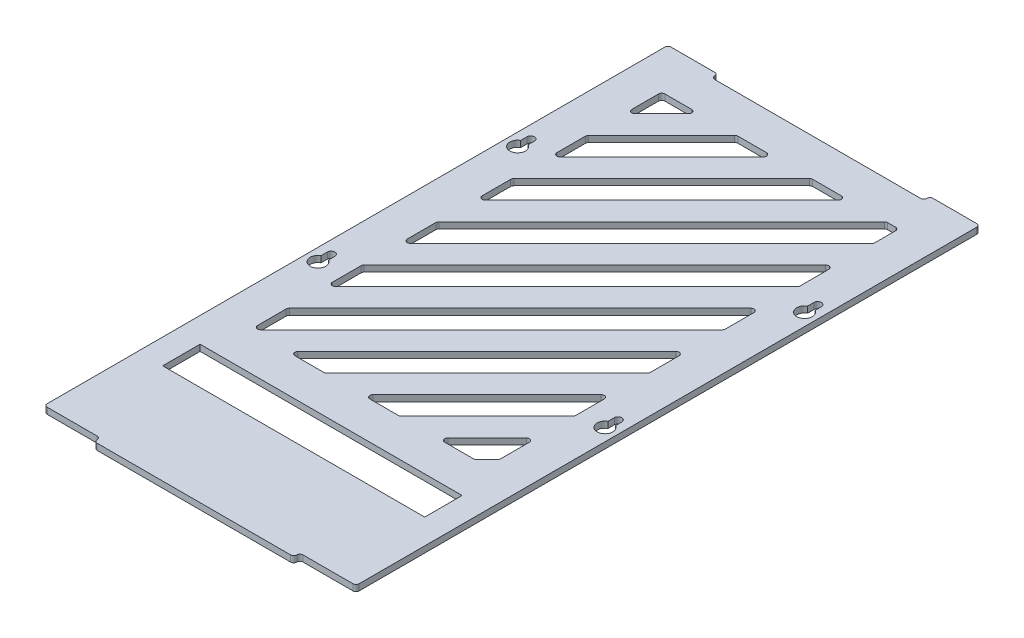
SolidWorks part; units mm, degrees
ref_plane "Front Plane" through (0, 0, 0) normal (0, 0, 1) x (1, 0, 0)
ref_plane "Top Plane" through (0, 0, 0) normal (0, 1, 0) x (1, 0, 0)
ref_plane "Right Plane" through (0, 0, 0) normal (1, 0, 0) x (0, 0, -1)
sketch "Sketch1" plane through (0, 0, 0) normal (0, 1, 0) x (1, 0, 0)
  line L0 (130.175, 0) -> (158.75, 0)
  line L1 (0, 0) -> (28.575, 0)
  line L2 (0, 0) -> (0, 317.5)
  line L3 (0, 317.5) -> (158.75, 317.5)
  line L4 (158.75, 0) -> (158.75, 317.5)
  line L6 (28.575, 0) -> (28.575, -3.175)
  line L7 (28.575, -3.175) -> (130.175, -3.175)
  line L8 (130.175, 0) -> (130.175, -3.175)
  point P9 (79.375, -3.175)
  point P10 (79.375, 317.5)
  dimension "D1" = 158.75
  dimension "D2" = 317.5
  dimension "D3" = 3.175
  dimension "D4" = 101.6
extrude "Boss-Extrude1" add sketch "Sketch1" along normal blind 3.175
sketch "Sketch2" plane through (0, 3.175, 0) normal (0, 1, 0) x (1, 0, 0)
  line L0 (158.75, 317.5) -> (0, 317.5) construction
  line L1 (25.4, 317.5) -> (133.35, 317.5)
  line L2 (25.4, 317.5) -> (25.4, 314.325)
  line L3 (25.4, 314.325) -> (133.35, 314.325)
  line L4 (133.35, 317.5) -> (133.35, 314.325)
  point P6 (79.375, 317.5)
  point P7 (79.375, 317.5)
  dimension "D1" = 107.95
  dimension "D2" = 3.175
extrude "Cut-Extrude1" cut sketch "Sketch2" against normal through all
sketch "Sketch3" plane through (0, 3.175, 0) normal (0, 1, 0) x (1, 0, 0)
  line L0 (25.4, 314.325) -> (133.35, 314.325) construction
  line L1 (12.7, 66.675) -> (146.05, 66.675)
  line L2 (12.7, 66.675) -> (12.7, 47.625)
  line L3 (12.7, 47.625) -> (146.05, 47.625)
  line L4 (146.05, 66.675) -> (146.05, 47.625)
  point P7 (79.375, 314.325)
  point P8 (79.375, 66.675)
  dimension "D1" = 133.35
  dimension "D2" = 19.05
  dimension "D3" = 47.625
extrude "Cut-Extrude2" cut sketch "Sketch3" against normal through all
fillet "Fillet1" radius 1.5875 12 edges at (25.4, 1.5875, -314.325) (25.4, 1.5875, -317.5) (0, 1.5875, -317.5) (0, 1.5875, 0) (28.575, 1.5875, 0) (28.575, 1.5875, 3.175) (130.175, 1.5875, 3.175) (130.175, 1.5875, 0) (158.75, 1.5875, 0) (158.75, 1.5875, -317.5) (133.35, 1.5875, -317.5) (133.35, 1.5875, -314.325)
sketch "Sketch4" plane through (0, 3.175, 0) normal (0, 1, 0) x (1, 0, 0)
  line L0 (6.35, 234.6325) -> (6.35, 241.3) construction
  line L1 (4.445, 238.1142) -> (4.445, 241.3)
  line L2 (8.255, 238.1142) -> (8.255, 241.3)
  line L3 (0, 315.9125) -> (0, 1.5875) construction
  line L4 (23.8125, 317.5) -> (1.5875, 317.5) construction
  arc A0 (4.445, 238.1142) -> (8.255, 238.1142) centre (6.35, 234.6325) ccw
  arc A1 (8.255, 241.3) -> (4.445, 241.3) centre (6.35, 241.3) ccw
  dimension "D2" = 7.9375
  dimension "D1" = 3.81
  dimension "D3" = 6.6675
  dimension "D4" = 6.35
  dimension "D5" = 76.2
extrude "Cut-Extrude3" cut sketch "Sketch4" against normal through all
pattern_linear "LPattern1" count 2 spacing 101.6 along (0, 0, 1) count 2 spacing 146.05 along (1, 0, 0) of "Cut-Extrude3"
sketch "Sketch5" plane through (0, 3.175, 0) normal (0, 1, 0) x (1, 0, 0)
  line L0 (146.05, 66.675) -> (12.7, 66.675) construction
  line L1 (12.7, 79.375) -> (146.05, 79.375) construction
  line L2 (12.7, 79.375) -> (12.7, 301.625) construction
  line L3 (12.7, 301.625) -> (146.05, 301.625) construction
  line L4 (146.05, 79.375) -> (146.05, 301.625) construction
  line L5 (26.9875, 314.325) -> (131.7625, 314.325) construction
  line L6 (19.05, 85.725) -> (19.05, 295.275)
  line L7 (19.05, 295.275) -> (139.7, 295.275)
  line L8 (139.7, 85.725) -> (139.7, 295.275)
  line L9 (19.05, 85.725) -> (139.7, 85.725)
  line L10 (19.05, 85.725) -> (139.7, 206.375)
  line L11 (19.05, 104.775) -> (139.7, 225.425)
  line L12 (19.05, 123.825) -> (139.7, 244.475)
  line L13 (19.05, 142.875) -> (139.7, 263.525)
  line L14 (19.05, 161.925) -> (139.7, 282.575)
  line L15 (19.05, 180.975) -> (139.7, 301.625)
  line L16 (19.05, 200.025) -> (139.7, 320.675)
  line L17 (19.05, 219.075) -> (139.7, 339.725)
  line L18 (19.05, 238.125) -> (139.7, 358.775)
  line L19 (19.05, 257.175) -> (139.7, 377.825)
  line L20 (19.05, 276.225) -> (139.7, 396.875)
  line L21 (19.05, 66.675) -> (139.7, 187.325)
  line L22 (19.05, 47.625) -> (139.7, 168.275)
  line L23 (19.05, 28.575) -> (139.7, 149.225)
  line L24 (19.05, 9.525) -> (139.7, 130.175)
  line L25 (19.05, -9.525) -> (139.7, 111.125)
  line L26 (19.05, -28.575) -> (139.7, 92.075)
  point P6 (79.375, 66.675)
  point P7 (79.375, 79.375)
  dimension "D1" = 133.35
  dimension "D2" = 12.7
  dimension "D3" = 12.7
  dimension "D5" = 45
  dimension "D4" = 6.35
  dimension "D6" = 11
  dimension "D7" = 7
extrude "Cut-Extrude4" cut sketch "Sketch5" against normal through all contours L9 L26 L8 L25 | L9 L24 L8 L23 | L9 L22 L8 L21 | L11 L6 L10 L8 | L13 L6 L12 L8 | L15 L6 L14 L8 L7 | L17 L6 L16 L7 | L19 L6 L18 L7 | L6 L20 L7 region at (79.375, 3.175, -155.575) region at (93.4983, 3.175, -131.9267) region at (79.375, 3.175, -193.675) region at (112.4324, 3.175, -112.9926) region at (78.8599, 3.175, -231.1943) region at (130.81, 3.175, -94.615) region at (62.0889, 3.175, -252.2361) region at (43.18, 3.175, -271.145) region at (25.4, 3.175, -288.925)
fillet "Fillet2" radius 1.5875 36 edges at (133.35, 1.5875, -85.725) (139.7, 1.5875, -92.075) (139.7, 1.5875, -111.125) (114.3, 1.5875, -85.725) (139.7, 1.5875, -130.175) (139.7, 1.5875, -149.225) (76.2, 1.5875, -85.725) (95.25, 1.5875, -85.725) (57.15, 1.5875, -85.725) (38.1, 1.5875, -85.725) (139.7, 1.5875, -168.275) (139.7, 1.5875, -187.325) (19.05, 1.5875, -85.725) (19.05, 1.5875, -104.775) (139.7, 1.5875, -206.375) (139.7, 1.5875, -225.425) (19.05, 1.5875, -123.825) (19.05, 1.5875, -142.875) (19.05, 1.5875, -161.925) (19.05, 1.5875, -180.975) (139.7, 1.5875, -244.475) (139.7, 1.5875, -263.525) (19.05, 1.5875, -200.025) (19.05, 1.5875, -219.075) (19.05, 1.5875, -238.125) (19.05, 1.5875, -257.175) (38.1, 1.5875, -295.275) (19.05, 1.5875, -276.225) (95.25, 1.5875, -295.275) (114.3, 1.5875, -295.275) (133.35, 1.5875, -295.275) (139.7, 1.5875, -282.575) (139.7, 1.5875, -295.275) (76.2, 1.5875, -295.275) (57.15, 1.5875, -295.275) (19.05, 1.5875, -295.275)
sketch "Sketch7" plane through (0, 3.175, 0) normal (0, 1, 0) x (1, 0, 0)
  line L0 (0, 0) -> (12.7, 0)
  line L2 (12.7, 66.675) -> (12.7, 47.625) construction
  line L3 (158.75, 0) -> (146.05, 0)
  line L4 (131.7625, 0) -> (157.1625, 0) construction
  line L5 (146.05, 47.625) -> (146.05, 66.675) construction
  line L6 (158.75, 1.5875) -> (158.75, 315.9125) construction
  line L7 (0, 19.05) -> (12.7, 19.05)
  line L8 (158.75, 19.05) -> (146.05, 19.05)
  line L9 (0, 38.1) -> (12.7, 38.1)
  line L10 (158.75, 38.1) -> (146.05, 38.1)
  line L11 (0, 57.15) -> (12.7, 57.15)
  line L12 (158.75, 57.15) -> (146.05, 57.15)
  line L13 (0, 76.2) -> (12.7, 76.2)
  line L14 (158.75, 76.2) -> (146.05, 76.2)
  line L15 (0, 95.25) -> (12.7, 95.25)
  line L16 (158.75, 95.25) -> (146.05, 95.25)
  line L17 (0, 114.3) -> (12.7, 114.3)
  line L18 (158.75, 114.3) -> (146.05, 114.3)
  line L19 (0, 133.35) -> (12.7, 133.35)
  line L20 (158.75, 133.35) -> (146.05, 133.35)
  line L21 (0, 152.4) -> (12.7, 152.4)
  line L22 (158.75, 152.4) -> (146.05, 152.4)
  line L23 (0, 171.45) -> (12.7, 171.45)
  line L24 (158.75, 171.45) -> (146.05, 171.45)
  line L25 (0, 190.5) -> (12.7, 190.5)
  line L26 (158.75, 190.5) -> (146.05, 190.5)
  line L27 (0, 209.55) -> (12.7, 209.55)
  line L28 (158.75, 209.55) -> (146.05, 209.55)
  line L29 (0, 228.6) -> (12.7, 228.6)
  line L30 (158.75, 228.6) -> (146.05, 228.6)
  line L31 (0, 247.65) -> (12.7, 247.65)
  line L32 (158.75, 247.65) -> (146.05, 247.65)
  line L33 (0, 266.7) -> (12.7, 266.7)
  line L34 (158.75, 266.7) -> (146.05, 266.7)
  line L35 (0, 285.75) -> (12.7, 285.75)
  line L36 (158.75, 285.75) -> (146.05, 285.75)
  dimension "D1" = 16
